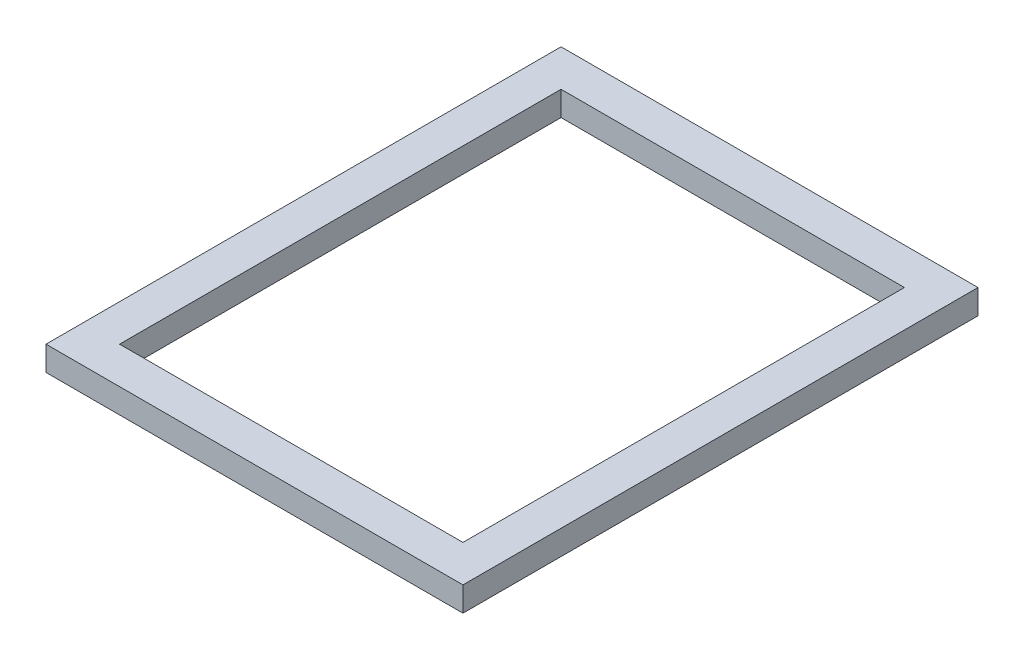
SolidWorks part; units mm, degrees
material "Silicon Rubber"
ref_plane "Front Plane" through (0, 0, 0) normal (0, 0, 1) x (1, 0, 0)
ref_plane "Top Plane" through (0, 0, 0) normal (0, 1, 0) x (1, 0, 0)
ref_plane "Right Plane" through (0, 0, 0) normal (1, 0, 0) x (0, 0, -1)
sketch "Sketch1" plane through (0, 0, 0) normal (0, 1, 0) x (1, 0, 0)
  line L0 (2.3813, 2.3813) -> (2.3813, 30.9562)
  line L1 (0, 0) -> (26.9875, 0)
  line L2 (0, 0) -> (0, 33.3374)
  line L3 (0, 33.3374) -> (26.9875, 33.3374)
  line L4 (26.9875, 0) -> (26.9875, 33.3374)
  line L5 (2.3813, 30.9562) -> (24.6062, 30.9562)
  line L6 (24.6062, 2.3813) -> (24.6062, 30.9562)
  line L7 (2.3813, 2.3813) -> (24.6062, 2.3813)
  dimension "D2" = 33.3374
  dimension "D3" = 26.9875
  dimension "D1" = 2.3813
extrude "Boss-Extrude1" add sketch "Sketch1" along normal blind 1.5875
